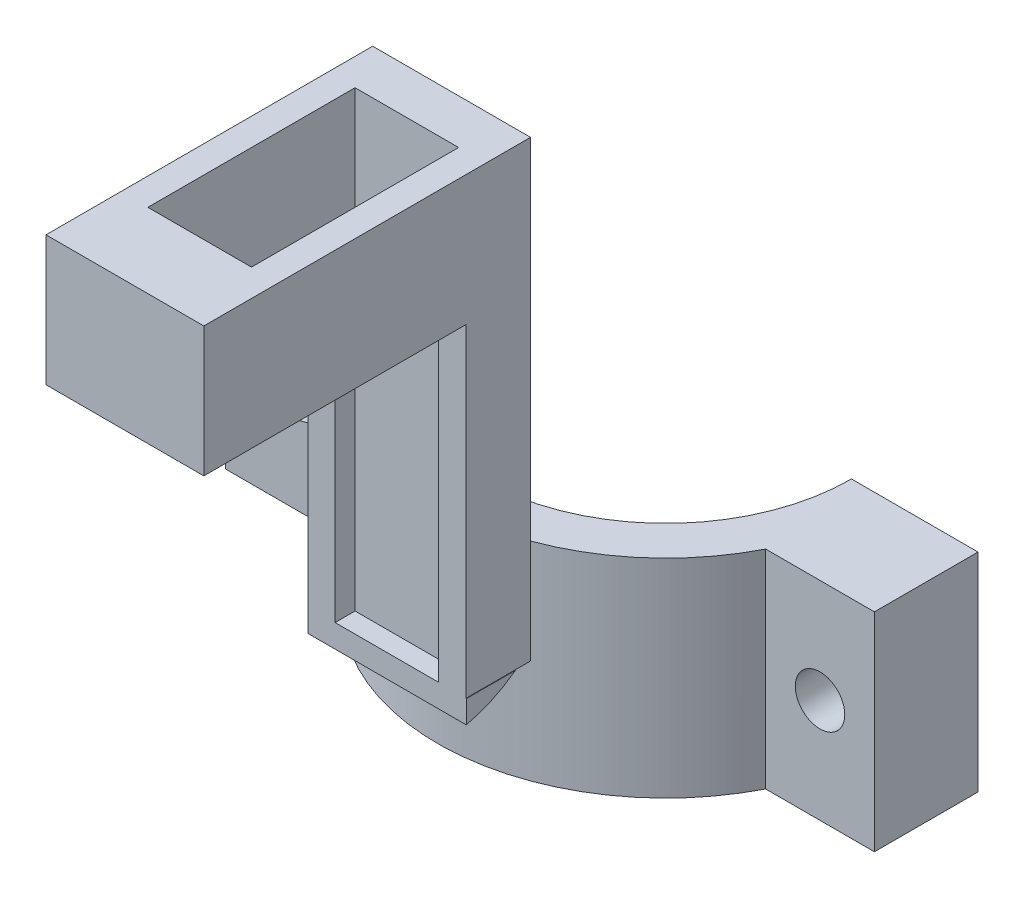
SolidWorks part; units mm, degrees
ref_plane "前基準面" through (0, 0, 0) normal (0, 0, 1) x (1, 0, 0)
ref_plane "上基準面" through (0, 0, 0) normal (0, 1, 0) x (1, 0, 0)
ref_plane "右基準面" through (0, 0, 0) normal (1, 0, 0) x (0, 0, -1)
sketch "草圖1" plane through (0, 0, 0) normal (0, 1, 0) x (1, 0, 0)
  circle A0 centre (0, 0) radius 14.34
  dimension "D1" = 28.68
extrude "伸長-薄件1" add sketch "草圖1" along normal blind 16.05 thin thin type one direction wall 3.29
ref_plane "平面1" through (17.75, 0, 0) normal (1, 0, 0) x (0, 0, -1)
sketch "草圖2" plane through (17.75, 0, 0) normal (1, 0, 0) x (0, 0, -1)
  line L0 (0, -983.95) -> (0, 49016.05) construction
  line L1 (14.34, 16.05) -> (-14.34, 16.05) construction
  line L2 (-1017.63, 8.025) -> (48982.37, 8.025) construction
  line L3 (-17.63, 16.05) -> (-17.63, 0) construction
  line L5 (-8, 16.05) -> (8, 16.05)
  line L6 (-8, 16.05) -> (-8, 0)
  line L7 (-8, 0) -> (8, 0)
  line L8 (8, 16.05) -> (8, 0)
  line L9 (-8, 16.05) -> (8, 0) construction
  line L10 (-8, 0) -> (8, 16.05) construction
  point P5 (0, 16.05)
  point P6 (0, 8.025)
  point P10 (-17.63, 8.025)
  dimension "D1" = 0
  dimension "D2" = 16
extrude "填料-伸長1" add sketch "草圖2" along normal blind 9.77 and the other way blind 3
sketch "草圖3" plane through (0, 16.05, 0) normal (0, 1, 0) x (1, 0, 0)
  line L0 (14.34, 0) -> (27.52, 0) construction
  line L1 (27.52, 8) -> (27.52, -8) construction
  line L2 (15.7104, -8) -> (27.52, -8) construction
  line L3 (27.52, 8) -> (24.11, 8)
  line L4 (27.52, 8) -> (27.52, -8)
  line L5 (27.52, -8) -> (24.11, -8)
  line L6 (24.11, 8) -> (24.11, -8)
  circle A0 centre (0, 0) radius 14.34 construction
  dimension "D1" = 3.41
extrude "除料-伸長1" cut sketch "草圖3" against normal through all
sketch "草圖4" plane through (0, 0, 8) normal (0, 0, 1) x (1, 0, 0)
  line L0 (19.9102, -983.95) -> (19.9102, 49016.05) construction
  line L1 (15.7104, 16.05) -> (24.11, 16.05) construction
  line L2 (-984.2896, 8.025) -> (49015.7104, 8.025) construction
  line L3 (15.7104, 0) -> (15.7104, 16.05) construction
  circle A0 centre (19.9102, 8.025) radius 1.91
  point P5 (19.9102, 16.05)
  point P10 (15.7104, 8.025)
  dimension "D1" = 3.82
extrude "除料-伸長2" cut sketch "草圖4" against normal through all
ref_plane "平面2" through (0, 0, 17.75) normal (0, 0, 1) x (1, 0, 0)
sketch "草圖5" plane through (0, 0, 17.75) normal (0, 0, 1) x (1, 0, 0)
  line L0 (-1017.63, 8.025) -> (48982.37, 8.025) construction
  line L1 (-17.63, 16.05) -> (-17.63, 0) construction
  line L2 (0, -983.95) -> (0, 49016.05) construction
  line L3 (14.34, 16.05) -> (-14.34, 16.05) construction
  line L5 (-6.095, 16.2886) -> (6.095, 16.2886)
  line L6 (-6.095, 16.2886) -> (-6.095, 8.025)
  line L7 (-6.095, 8.025) -> (6.095, 8.025)
  line L8 (6.095, 16.2886) -> (6.095, 8.025)
  line L9 (-6.095, 16.2886) -> (6.095, 8.025) construction
  line L10 (-6.095, 8.025) -> (6.095, 16.2886) construction
  point P5 (-17.63, 8.025)
  point P6 (0, 12.1568)
  point P10 (0, 16.05)
  dimension "D1" = 12.19
extrude "填料-伸長2" add sketch "草圖5" along normal blind 4 and the other way blind 2.77
sketch "草圖6" plane through (0, 16.2886, 0) normal (0, 1, 0) x (1, 0, 0)
  line L1 (-6.095, -14.98) -> (6.095, -14.98)
  line L2 (-6.095, -14.98) -> (-6.095, -21.75)
  line L3 (-6.095, -21.75) -> (6.095, -21.75)
  line L4 (6.095, -14.98) -> (6.095, -21.75)
extrude "填料-伸長3" add sketch "草圖6" along normal blind 63
sketch "草圖8" plane through (0, 79.2886, 0) normal (0, 1, 0) x (1, 0, 0)
  line L1 (-6.095, -21.75) -> (6.095, -21.75)
  line L2 (-6.095, -21.75) -> (-6.095, -14.98)
  line L3 (-6.095, -14.98) -> (6.095, -14.98)
  line L4 (6.095, -21.75) -> (6.095, -14.98)
extrude "填料-伸長4" add sketch "草圖8" along normal blind 0.16
ref_plane "平面3" through (-17.75, 0, 0) normal (1, 0, 0) x (0, 0, -1)
sketch "草圖12" plane through (-17.75, 0, 0) normal (1, 0, 0) x (0, 0, -1)
  line L0 (0.5435, -983.95) -> (0.5435, 49016.05) construction
  line L1 (17.63, 16.05) -> (-16.5429, 16.05) construction
  line L2 (-982.37, 8.025) -> (49017.63, 8.025) construction
  line L3 (17.63, 0) -> (17.63, 16.05) construction
  line L5 (8.5435, 16.05) -> (-7.4565, 16.05)
  line L6 (8.5435, 16.05) -> (8.5435, 0)
  line L7 (8.5435, 0) -> (-7.4565, 0)
  line L8 (-7.4565, 16.05) -> (-7.4565, 0)
  line L9 (8.5435, 16.05) -> (-7.4565, 0) construction
  line L10 (8.5435, 0) -> (-7.4565, 16.05) construction
  point P5 (0.5435, 16.05)
  point P6 (0.5435, 8.025)
  point P10 (17.63, 8.025)
  dimension "D1" = 0
  dimension "D2" = 16
extrude "填料-伸長5" add sketch "草圖12" along normal blind 3.16 and the other way blind 10
sketch "草圖13" plane through (0, 16.05, 0) normal (0, 1, 0) x (1, 0, 0)
  line L0 (-14.34, 0) -> (-27.75, 0) construction
  line L1 (-27.75, 8.5435) -> (-27.75, -7.4565) construction
  line L2 (-27.75, -7.4565) -> (-15.9755, -7.4565) construction
  line L3 (-27.75, 8.5435) -> (-26.54, 8.5435)
  line L4 (-27.75, 8.5435) -> (-27.75, -7.4565)
  line L5 (-27.75, -7.4565) -> (-26.54, -7.4565)
  line L6 (-26.54, 8.5435) -> (-26.54, -7.4565)
  circle A0 centre (0, 0) radius 14.34 construction
  dimension "D1" = 1.21
extrude "除料-伸長3" cut sketch "草圖13" against normal through all
sketch "草圖14" plane through (0, 0, -8.5435) normal (0, 0, -1) x (-1, 0, 0)
  line L0 (20.9808, -983.95) -> (20.9808, 49016.05) construction
  line L1 (26.54, 16.05) -> (15.4216, 16.05) construction
  line L2 (-973.46, 8.025) -> (49026.54, 8.025) construction
  line L3 (26.54, 0) -> (26.54, 16.05) construction
  circle A0 centre (20.9808, 8.025) radius 1.91
  point P5 (20.9808, 16.05)
  point P10 (26.54, 8.025)
  dimension "D1" = 3.82
extrude "除料-伸長4" cut sketch "草圖14" against normal through all
sketch "草圖15" plane through (0, 79.4486, 0) normal (0, 1, 0) x (1, 0, 0)
  line L0 (6.095, -14.98) -> (-6.095, -14.98) construction
  circle A0 centre (0, -14.98) radius 4.05
  dimension "D1" = 8.1
extrude "除料-伸長5" cut sketch "草圖15" against normal blind 24
sketch "草圖16" plane through (0, 16.05, 0) normal (0, 1, 0) x (1, 0, 0)
  line L0 (24.11, 8) -> (24.11, -8) construction
  line L1 (24.11, 0) -> (-32.2905, 0)
  line L2 (24.11, 0) -> (24.11, 19.935)
  line L3 (24.11, 19.935) -> (-32.2905, 19.935)
  line L4 (-32.2905, 0) -> (-32.2905, 19.935)
extrude "除料-伸長6" cut sketch "草圖16" against normal through all
sketch "草圖17" plane through (0, 0, 21.75) normal (0, 0, 1) x (1, 0, 0)
  line L1 (-6.095, 8.025) -> (6.095, 8.025)
  line L2 (-6.095, 8.025) -> (-6.095, 79.4486)
  line L3 (-6.095, 79.4486) -> (6.095, 79.4486)
  line L4 (6.095, 8.025) -> (6.095, 79.4486)
extrude "填料-伸長7" add sketch "草圖17" along normal blind 25
sketch "草圖18" plane through (-6.095, 0, 0) normal (-1, 0, 0) x (0, 0, 1)
  line L0 (14.98, 79.4486) -> (46.75, 79.4486) construction
  line L1 (14.98, 16.05) -> (41.7734, 16.05)
  line L2 (14.98, 16.05) -> (14.98, 79.4486)
  line L3 (14.98, 79.4486) -> (41.7734, 79.4486)
  line L4 (41.7734, 16.05) -> (41.7734, 79.4486)
extrude "除料-伸長7" cut sketch "草圖18" against normal blind 25
sketch "草圖19" plane through (0, 79.4486, 0) normal (0, 1, 0) x (1, 0, 0)
  line L0 (6.095, -41.7734) -> (-6.095, -41.7734) construction
  circle A0 centre (0, -41.7734) radius 4
  dimension "D1" = 8
extrude "除料-伸長8" cut sketch "草圖19" against normal blind 24
sketch "草圖20" plane through (6.095, 0, 0) normal (1, 0, 0) x (0, 0, -1)
  line L0 (-41.7734, 16.05) -> (-41.7734, 8.025)
  line L1 (-16.5429, 8.025) -> (-46.75, 8.025) construction
  line L2 (-41.7734, 8.025) -> (-46.75, 8.025)
  line L3 (-46.75, 8.025) -> (-46.75, 79.4486)
  line L4 (-46.75, 79.4486) -> (-41.7734, 79.4486)
  line L5 (-41.7734, 79.4486) -> (-41.7734, 16.05)
extrude "除料-伸長9" cut sketch "草圖20" against normal blind 29
sketch "草圖23" plane through (0, 8.025, 0) normal (0, -1, 0) x (1, 0, 0)
  line L0 (-6.095, 41.7734) -> (-6.095, 17.75)
  line L1 (23.6775, 17.75) -> (-23.6775, 17.75) construction
  line L2 (-6.095, 16.5429) -> (-6.095, 41.7734) construction
  line L3 (-6.095, 17.75) -> (6.1383, 17.75)
  line L4 (6.1383, 17.75) -> (6.095, 41.7734)
  line L5 (6.095, 41.7734) -> (-6.095, 41.7734)
extrude "填料-伸長9" add sketch "草圖23" along normal blind 2
fillet "圓角1" radius 10 1 edges at (0.0216, 6.025, 17.75)
sketch "草圖24" plane through (0, 16.05, 0) normal (0, 1, 0) x (1, 0, 0)
  line L0 (6.095, -41.7734) -> (6.095, -16.5429) construction
  line L1 (-6.095, -16.5429) -> (6.095, -16.5429)
  line L2 (-6.095, -16.5429) -> (-6.095, -21.5429)
  line L3 (-6.095, -21.5429) -> (6.095, -21.5429)
  line L4 (6.095, -16.5429) -> (6.095, -21.5429)
  dimension "D1" = 5
extrude "填料-伸長10" add sketch "草圖24" along normal blind 27
sketch "草圖25" plane through (-6.095, 0, 0) normal (-1, 0, 0) x (0, 0, 1)
  line L0 (21.5429, 16.05) -> (41.7734, 16.05)
  line L1 (41.7734, 16.05) -> (41.7734, 6.025)
  line L2 (41.7734, 6.025) -> (21.5429, 6.025)
  line L3 (21.5429, 6.025) -> (21.5429, 16.05)
sketch "草圖27" plane through (0, 0, 21.5429) normal (0, 0, 1) x (1, 0, 0)
  line L0 (6.095, 43.05) -> (6.095, 16.05) construction
  line L1 (-6.095, 43.05) -> (6.095, 43.05)
  line L2 (-6.095, 43.05) -> (-6.095, 33.02)
  line L3 (-6.095, 33.02) -> (6.095, 33.02)
  line L4 (6.095, 43.05) -> (6.095, 33.02)
  dimension "D1" = 10.03
extrude "填料-伸長11" add sketch "草圖27" along normal blind 20.23
sketch "草圖21" plane through (0, 16.05, 0) normal (0, 1, 0) x (1, 0, 0)
  line L0 (0, -1014.34) -> (0, 48985.66) construction
  line L2 (-4, -20) -> (4, -20)
  line L3 (-4, -20) -> (-4, -36)
  line L4 (-4, -36) -> (4, -36)
  line L5 (4, -20) -> (4, -36)
  line L6 (-4, -20) -> (4, -36) construction
  line L7 (-4, -36) -> (4, -20) construction
  arc A0 (-14.34, 0) -> (14.34, 0) centre (0, 0) ccw construction
  point P1 (0, -28)
  point P6 (0, -14.34)
  dimension "D1" = 20
  dimension "D2" = 16
  dimension "D3" = 8
extrude "除料-伸長10" cut sketch "草圖21" against normal blind 8 and the other way blind 45.23
extrude "除料-伸長12" cut sketch "草圖25" against normal blind 20.23
sketch "草圖31" plane through (0, 0, 36) normal (0, 0, -1) x (-1, 0, 0)
  line L0 (4, 43.05) -> (4, 33.02) construction
  line L1 (-4, 33.02) -> (4, 33.02)
  line L2 (-4, 33.02) -> (-4, 35.05)
  line L3 (-4, 35.05) -> (4, 35.05)
  line L4 (4, 33.02) -> (4, 35.05)
  dimension "D1" = 2.03
extrude "填料-伸長13" add sketch "草圖31" along normal blind 16.23
